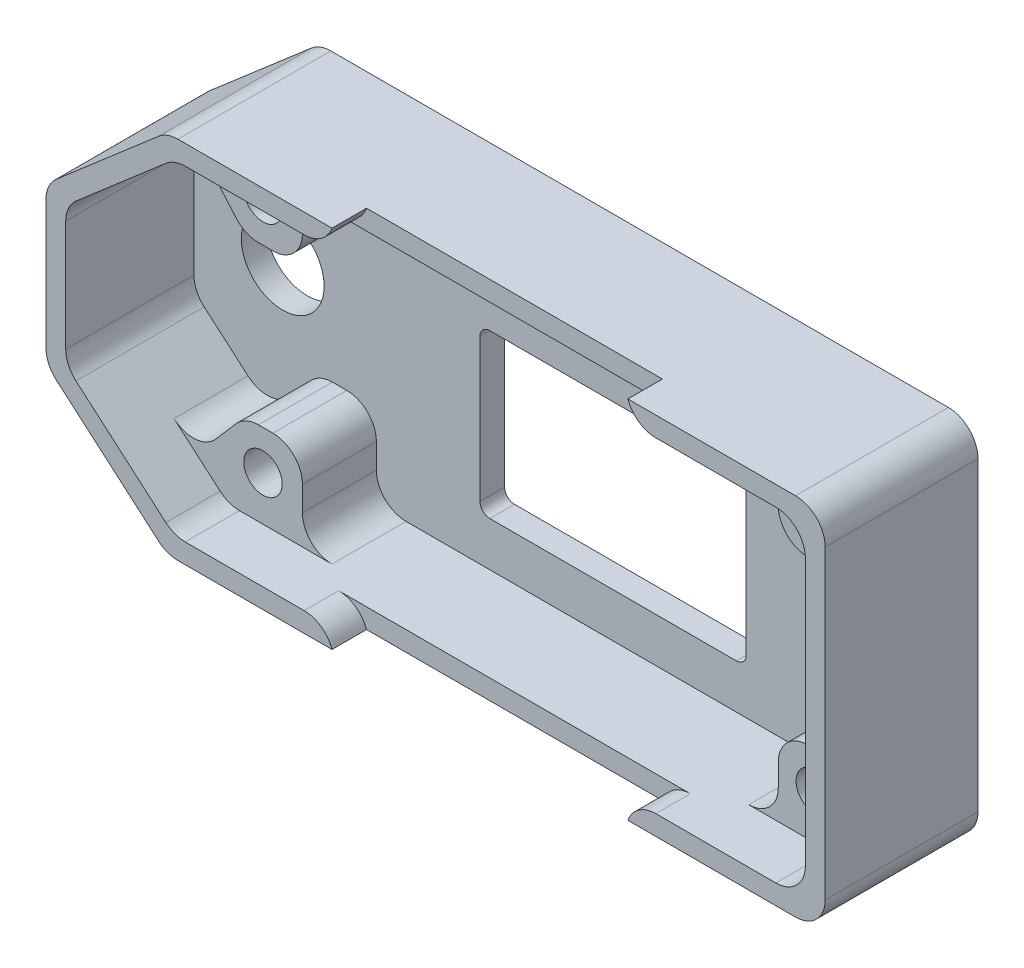
SolidWorks part; units mm, degrees
ref_plane "Front Plane" through (0, 0, 0) normal (0, 0, 1) x (1, 0, 0)
ref_plane "Top Plane" through (0, 0, 0) normal (0, 1, 0) x (1, 0, 0)
ref_plane "Right Plane" through (0, 0, 0) normal (1, 0, 0) x (0, 0, -1)
sketch "Sketch1" plane through (0, 0, 0) normal (0, 0, 1) x (1, 0, 0)
  line L1 (0, 0) -> (79, 0)
  line L2 (0, 0) -> (0, 37)
  line L3 (0, 37) -> (79, 37)
  line L4 (79, 0) -> (79, 37)
  dimension "D1" = 79
  dimension "D2" = 37
extrude "Boss-Extrude1" add sketch "Sketch1" against normal blind 20
sketch "Sketch2" plane through (0, 0, 0) normal (0, 0, 1) x (1, 0, 0)
  line L0 (79, 0) -> (79, 37) construction
  line L1 (77, 35) -> (13, 35)
  line L2 (77, 35) -> (77, 2)
  line L3 (77, 2) -> (13, 2)
  line L5 (0, 0) -> (79, 0) construction
  line L6 (79, 37) -> (0, 37) construction
  line L7 (13, 35) -> (2, 25.5)
  line L8 (2, 25.5) -> (2, 11.5)
  line L9 (2, 11.5) -> (13, 2)
  line L10 (0, 37) -> (0, 0) construction
  dimension "D1" = 2
  dimension "D2" = 2
  dimension "D3" = 2
  dimension "D4" = 2
  dimension "D5" = 11
  dimension "D6" = 9.5
  dimension "D7" = 9.5
  dimension "D8" = 11
extrude "Cut-Extrude1" cut sketch "Sketch2" against normal blind 17.5
sketch "Sketch3" plane through (0, 0, 0) normal (0, 0, 1) x (1, 0, 0)
  line L0 (12.2559, 37) -> (0, 26.4154)
  line L1 (79, 37) -> (0, 37) construction
  line L2 (0, 37) -> (0, 0) construction
  line L3 (0, 26.4154) -> (0, 37)
  line L4 (0, 37) -> (12.2559, 37)
  line L5 (0, 0) -> (79, 0) construction
  line L6 (12.2559, 0) -> (0, 10.5846)
  line L7 (0, 10.5846) -> (0, 0)
  line L8 (0, 0) -> (12.2559, 0)
  line L9 (2, 11.5) -> (13, 2) construction
  line L10 (13, 35) -> (2, 25.5) construction
  dimension "D1" = 2
  dimension "D2" = 2
extrude "Cut-Extrude2" cut sketch "Sketch3" against normal up to surface (20 mm away) up to face at (39.5, 18.5, -20)
sketch "Sketch4" plane through (0, 0, -17.5) normal (0, 0, 1) x (1, 0, 0)
  line L0 (77, 2) -> (77, 35) construction
  line L1 (77, 35) -> (68.75, 35)
  line L2 (77, 35) -> (77, 26.75)
  line L3 (77, 26.75) -> (68.75, 26.75)
  line L4 (68.75, 35) -> (68.75, 26.75)
  line L5 (13, 35) -> (20.5, 35)
  line L9 (13, 2) -> (20.5, 2)
  line L12 (20.5, 2) -> (20.5, 35)
  line L13 (77, 2) -> (68.75, 2)
  line L14 (77, 2) -> (77, 10.25)
  line L15 (77, 10.25) -> (68.75, 10.25)
  line L16 (68.75, 2) -> (68.75, 10.25)
  line L17 (13, 35) -> (2, 25.5) construction
  line L18 (77, 35) -> (13, 35) construction
  line L19 (13, 2) -> (77, 2) construction
  line L20 (2, 25.5) -> (2, 11.5) construction
  line L21 (2, 25.5) -> (13, 35)
  line L22 (2, 11.5) -> (13, 2) construction
  line L23 (13, 2) -> (2, 11.5)
  line L24 (2, 25.5) -> (2, 11.5) construction
  line L25 (2, 11.5) -> (13, 2) construction
  line L26 (2, 25.5) -> (2, 11.5)
  point P22 (77, 18.5)
  point P25 (45, 35)
  point P28 (45, 2)
  dimension "D1" = 8.25
  dimension "D2" = 8.25
  dimension "D3" = 23.75
  dimension "D4" = 23.75
  dimension "D5" = 24.5
extrude "Boss-Extrude2" add sketch "Sketch4" along normal blind 7.5
sketch "Sketch5" plane through (0, 0, -10) normal (0, 0, 1) x (1, 0, 0)
  line L0 (77, 10.25) -> (77, 26.75) construction
  line L5 (2, 25.5) -> (2, 11.5) construction
  line L8 (77, 35) -> (13, 35) construction
  line L9 (13, 2) -> (77, 2) construction
  circle A0 centre (16.5, 30.5) radius 1.95
  circle A1 centre (72.5, 30.5) radius 1.95
  circle A2 centre (72.5, 6.5) radius 1.95
  circle A3 centre (16.5, 6.5) radius 1.95
  point P10 (77, 18.5)
  point P13 (45, 35)
  point P18 (45, 2)
  point P19 (2, 18.5)
  dimension "D1" = 3.9
  dimension "D2" = 3.9
  dimension "D3" = 3.9
  dimension "D4" = 3.9
  dimension "D5" = 24
  dimension "D7" = 56
  dimension "D8" = 56
  dimension "D9" = 27.5
  dimension "D10" = 28.5
  dimension "D11" = 24
  dimension "D12" = 12
  dimension "D13" = 28.5
  dimension "D14" = 27.5
  dimension "D6" = 12
extrude "Cut-Extrude3" cut sketch "Sketch5" against normal blind 5.5
sketch "Sketch6" plane through (0, 0, -10) normal (0, 0, 1) x (1, 0, 0)
  circle A0 centre (11, 18.5) radius 4.2
  circle A1 centre (16.5, 30.5) radius 1.95 construction
  dimension "D1" = 5.5
  dimension "D2" = 12
  dimension "D3" = 8.4
extrude "Cut-Extrude4" cut sketch "Sketch6" against normal up to surface (10 mm away) up to face at (30.4186, 18.5, -20)
sketch "Sketch7" plane through (0, 0, -17.5) normal (0, 0, 1) x (1, 0, 0)
  line L1 (31, 23) -> (58, 23)
  line L2 (31, 23) -> (31, 6.5)
  line L3 (31, 6.5) -> (58, 6.5)
  line L4 (58, 23) -> (58, 6.5)
  circle A0 centre (72.5, 30.5) radius 1.95 construction
  circle A1 centre (72.5, 6.5) radius 1.95 construction
  point P6 (44.5, 23)
  dimension "D1" = 0
  dimension "D2" = 28
  dimension "D3" = 7.5
  dimension "D4" = 27
extrude "Cut-Extrude5" cut sketch "Sketch7" against normal up to surface (2.5 mm away) up to face at (6.8, 18.5, -20)
sketch "Sketch12" plane through (0, 0, -10) normal (0, 0, 1) x (1, 0, 0)
  line L0 (9.7514, 32.1944) -> (14.6693, 26.5)
  line L1 (20.5, 26.5) -> (20.5, 10.5)
  line L3 (14.6693, 26.5) -> (20.5, 26.5)
  line L5 (13, 35) -> (2, 25.5) construction
  line L6 (2, 11.5) -> (13, 2) construction
  line L7 (20.5, 2) -> (20.5, 35) construction
  line L8 (13, 35) -> (2, 25.5) construction
  line L9 (20.5, 2) -> (20.5, 35) construction
  line L12 (20.5, 10.5) -> (14.6693, 10.5)
  line L13 (9.7514, 4.8056) -> (14.6693, 10.5)
  line L17 (9.7514, 32.1944) -> (2, 25.5)
  line L18 (2, 25.5) -> (2, 11.5)
  line L19 (2, 11.5) -> (9.7514, 4.8056)
  circle A2 centre (16.5, 30.5) radius 1.95 construction
  circle A3 centre (16.5, 6.5) radius 1.95 construction
  dimension "D3" = 4
  dimension "D4" = 4
  dimension "D1" = 4
  dimension "D2" = 4
extrude "Cut-Extrude10" cut sketch "Sketch12" against normal up to surface (7.5 mm away) up to face at (44.5, 14.75, -17.5)
sketch "Sketch13" plane through (0, 0, 0) normal (0, 0, 1) x (1, 0, 0)
  line L1 (0, 0) -> (79, 0)
  line L2 (0, 0) -> (0, 37)
  line L3 (0, 37) -> (79, 37)
  line L4 (79, 0) -> (79, 37)
  dimension "D1" = 79
  dimension "D2" = 37
extrude "Cut-Extrude11" cut sketch "Sketch13" against normal blind 4.5
sketch "Sketch14" plane through (0, 0, -4.5) normal (0, 0, 1) x (1, 0, 0)
  line L0 (79, 37) -> (12.2559, 37) construction
  line L1 (29, 37) -> (59, 37)
  line L2 (29, 37) -> (29, 35)
  line L3 (29, 35) -> (59, 35)
  line L4 (59, 37) -> (59, 35)
  line L5 (68.75, 35) -> (20.5, 35) construction
  line L6 (13, 2) -> (77, 2) construction
  line L7 (29, 2) -> (59, 2)
  line L8 (29, 2) -> (29, 0)
  line L9 (29, 0) -> (59, 0)
  line L10 (59, 2) -> (59, 0)
  line L11 (12.2559, 0) -> (79, 0) construction
  line L12 (79, 0) -> (79, 37) construction
  point P16 (44, 35)
  point P19 (44, 2)
  dimension "D1" = 35
  dimension "D2" = 30
  dimension "D3" = 35
  dimension "D4" = 30
extrude "Cut-Extrude12" cut sketch "Sketch14" against normal blind 3.5
sketch "Sketch9" plane through (0, 0, -17.5) normal (0, 0, 1) x (1, 0, 0)
  line L1 (71.5, 11.25) -> (75, 11.25)
  line L2 (71.5, 11.25) -> (71.5, 26.25)
  line L3 (71.5, 26.25) -> (75, 26.25)
  line L4 (75, 11.25) -> (75, 26.25)
  line L5 (77, 10.25) -> (77, 26.75) construction
  circle A0 centre (72.5, 30.5) radius 1.95 construction
  dimension "D1" = 3.5
  dimension "D2" = 2
  dimension "D3" = 15
  dimension "D4" = 4.25
extrude "Cut-Extrude7" cut sketch "Sketch9" against normal up to surface (2.5 mm away) up to face at (44.5, 14.75, -20)
fillet "Fillet2" radius 3 6 edges at (20.5, 2, -13.75) (68.75, 2, -13.75) (77, 10.25, -13.75) (77, 26.75, -13.75) (68.75, 35, -13.75) (20.5, 35, -13.75)
fillet "Fillet18" radius 3 4 edges at (20.5, 10.5, -13.75) (20.5, 26.5, -13.75) (68.75, 10.25, -13.75) (68.75, 26.75, -13.75)
fillet "Fillet19" radius 3 4 edges at (14.6693, 10.5, -13.75) (14.6693, 26.5, -13.75) (9.7514, 4.8056, -13.75) (9.7514, 32.1944, -13.75)
fillet "Fillet11" radius 3 6 edges at (79, 37, -12.25) (79, 0, -12.25) (12.2559, 0, -12.25) (0, 10.5846, -12.25) (0, 26.4154, -12.25) (12.2559, 37, -12.25)
fillet "Fillet12" radius 1 4 edges at (58, 23, -18.75) (31, 23, -18.75) (58, 6.5, -18.75) (31, 6.5, -18.75)
fillet "Fillet14" radius 3 4 edges at (59, 2, -6.25) (29, 2, -6.25) (59, 35, -6.25) (29, 35, -6.25)
fillet "Fillet15" radius 3 4 edges at (77, 2, -7.25) (77, 35, -7.25) (13, 35, -7.25) (13, 2, -7.25)
fillet "Fillet13" radius 1 4 edges at (75, 26.25, -18.75) (71.5, 26.25, -18.75) (75, 11.25, -18.75) (71.5, 11.25, -18.75)
fillet "Fillet20" radius 3 2 edges at (2, 11.5, -11) (2, 25.5, -11)
